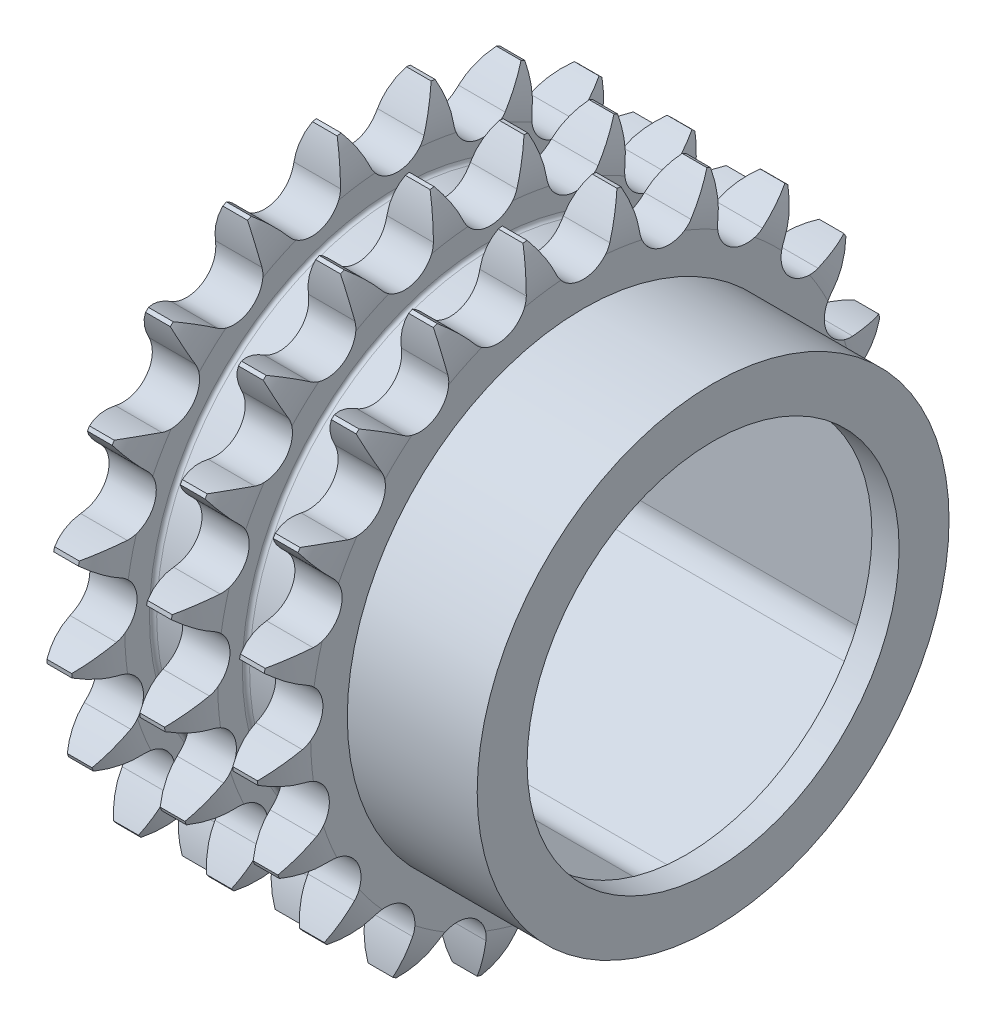
SolidWorks part; units mm, degrees
material "1.0503 (C45)"
ref_plane "Plane1" through (0, 0, 0) normal (0, 0, 1) x (1, 0, 0)
ref_plane "Plane2" through (0, 0, 0) normal (0, 1, 0) x (1, 0, 0)
ref_plane "Plane3" through (0, 0, 0) normal (1, 0, 0) x (0, 0, -1)
sketch "Clipboard" plane through (0, 0, 0) normal (0, 1, 0) x (1, 0, 0)
  line L0 (0, 0) -> (8.8924, -3.4135)
  line L1 (-15, 0) -> (100, 0) construction
  line L2 (0, 0) -> (-0.8203, 0.9272)
  line L3 (0, 0) -> (-8.8973, 3.4006)
  line L4 (0, 0) -> (2.8941, 1.1109)
  line L5 (0, 0) -> (-46.8476, -17.4728)
  line L6 (0, 0) -> (-21.2921, -14.3658)
  line L7 (-0.8203, 0.9272) -> (44.8574, 21.2642)
  line L8 (-76.2, 38.1) -> (-75.5, 38.1)
  line L9 (-73.319, 40.6764) -> (-72.9207, 40.7126)
  line L10 (-73.4529, 9.1872) -> (-63.2129, 9.1872)
  circle A0 centre (0, 0) radius 3.175
  circle A1 centre (0, 0) radius 26.8806
  circle A2 centre (0, 0) radius 37.5
  dimension "Dr" = 6.35
  dimension "MHD" = 53.7612
  dimension "Hub_dia" = 75
  dimension "Num_teeth" = 21
  dimension "Pitch" = 9.525
  dimension "Width" = 3.1
  dimension "Side_relief" = 1.238
  dimension "Side_radius" = 9.525
  dimension "Overall_len" = 50
  dimension "Show_teeth" = 21
  dimension "Thickness" = 25.6852
  dimension "OAL" = 50.0005
  dimension "T_dim" = 0.7
  dimension "Fillet_rad" = 0.4
  dimension "Face_width" = 5.205
  dimension "Num_strands" = 3
  dimension "Transv_pitch" = 10.24
  dimension "Plate_wid" = 8.26
sketch "BasProSke" plane through (0, 0, 0) normal (0, 1, 0) x (1, 0, 0)
  line L0 (-10, 0) -> (60, 0) construction
  line L1 (0, 0) -> (0, 30.0363)
  line L2 (0, 0) -> (25.6852, 0)
  line L3 (25.6852, 0) -> (25.6852, 30.0363)
  line L4 (24.4472, 34.7321) -> (1.238, 34.7321)
  arc A0 (0, 30.0363) -> (1.238, 34.7321) centre (9.525, 30.0363) cw
  arc A1 (25.6852, 30.0363) -> (24.4472, 34.7321) centre (16.1602, 30.0363) ccw
  dimension "Thickness" = 25.6852
  dimension "D1" = 9.525
  dimension "G1" = 1.238
  dimension "G2" = 1.238
  dimension "Diameter" = 69.4643
revolve "Base-Revolve" add sketch "BasProSke" angle 360 about L0
sketch "GrvSke" plane through (0, 0, 0) normal (0, 1, 0) x (1, 0, 0)
  line L0 (5.2052, 30.0363) -> (5.2052, 27.3219)
  line L1 (5.6052, 26.9219) -> (9.84, 26.9219)
  line L2 (10.24, 27.3219) -> (10.24, 30.0363)
  line L3 (3.9672, 34.7321) -> (11.478, 34.7321)
  line L4 (7.7226, 0) -> (7.7226, 52.07) construction
  line L5 (-10, 0) -> (60, 0) construction
  line L6 (0, 0) -> (35.56, 0) construction
  arc A0 (10.24, 30.0363) -> (11.478, 34.7321) centre (19.765, 30.0363) cw
  arc A1 (5.2052, 30.0363) -> (3.9672, 34.7321) centre (-4.3198, 30.0363) ccw
  arc A2 (5.2052, 27.3219) -> (5.6052, 26.9219) centre (5.6052, 27.3219) ccw
  arc A3 (9.84, 26.9219) -> (10.24, 27.3219) centre (9.84, 27.3219) ccw
  dimension "Fillet_rad" = 0.4
  dimension "D1" = 9.525
  dimension "G1" = 1.238
  dimension "Diameter" = 69.4643
  dimension "Grv_diam" = 53.8438
  dimension "Offset" = 7.7226
  dimension "Grv_width" = 5.0348
revolve "Groove" cut sketch "GrvSke" angle 360 about L6
pattern_linear "Grooves" count 2 spacing 10.24 along (1, 0, 0) of "Groove"
sketch "TooCutSke" plane through (0, 0, 0) normal (1, 0, 0) x (0, 0, -1)
  line L0 (0, 31.9858) -> (2.9702, 30.7771) construction
  line L1 (0, 0) -> (0, 107) construction
  line L2 (0, 31.9858) -> (-10, 31.9858) construction
  line L3 (0, 31.9858) -> (-2.9702, 30.7771) construction
  arc A0 (2.9702, 30.7771) -> (5.2931, 34.8323) centre (19.2036, 24.1712) cw
  arc A1 (2.9702, 30.7771) -> (-2.9702, 30.7771) centre (0, 31.9858) cw
  arc A2 (-2.9702, 30.7771) -> (-5.2931, 34.8323) centre (-19.2036, 24.1712) ccw
  arc A3 (5.2931, 34.8323) -> (-5.2931, 34.8323) centre (0, 0) ccw
  dimension "R1" = 3.2067
  dimension "R2" = 17.526
  dimension "Overcut" = 35.2321
  dimension "Seat_radius" = 31.9858
  dimension "X" = 135.714
extrude "ToothCut" cut sketch "TooCutSke" along normal through all
pattern_circular "TeethCuts" count 21 every 17.143 about axis through (-10, 0, 0) along (1, 0, 0) of "ToothCut"
sketch "HubNeaOneSke" plane through (0, 0, 0) normal (-1, 0, 0) x (0, 0, 1)
  circle A0 centre (0, 0) radius 26.8806
  dimension "Diameter" = 53.7612
extrude "HubNearOne" [suppressed] add sketch "HubNeaOneSke" along normal blind 24.3153
fillet "HubNearOneFillet" [suppressed] radius 0.4
sketch "HubNeaBotSke" plane through (0, 0, 0) normal (-1, 0, 0) x (0, 0, 1)
  circle A0 centre (0, 0) radius 26.8806
  dimension "Diameter" = 53.7612
extrude "HubNearBoth" [suppressed] add sketch "HubNeaBotSke" along normal blind 12.1577
fillet "HubNearBothFillet" [suppressed] radius 0.4
ref_plane "FarPln" through (25.6852, 0, 0) normal (1, 0, 0) x (0, 0, -1)
sketch "HubFarSke" plane through (25.6852, 0, 0) normal (1, 0, 0) x (0, 0, -1)
  circle A0 centre (0, 0) radius 26.8806
  dimension "Diameter" = 53.7612
extrude "HubFar" [suppressed] add sketch "HubFarSke" along normal blind 12.1577
fillet "HubFarFillet" [suppressed] radius 0.4
sketch "BorSke" plane through (0, 0, 0) normal (1, 0, 0) x (0, 0, -1)
  circle A0 centre (0, 0) radius 2
  dimension "Diameter" = 4
extrude "Bore" cut sketch "BorSke" along normal mid plane 100.001
sketch "KeySke" plane through (0, 0, 0) normal (1, 0, 0) x (0, 0, -1)
  line L0 (-0.8, 0) -> (-0.8, 2.7)
  line L1 (-0.8, 2.7) -> (0.8, 2.7)
  line L2 (0.8, 2.7) -> (0.8, 0)
  line L3 (0, 0) -> (0, 34) construction
  line L4 (-0.8, 0) -> (0.8, 0)
  dimension "Offset" = 2.7
  dimension "Width" = 1.6
extrude "Keyway" [suppressed] cut sketch "KeySke" along normal mid plane 100.001
pattern_circular "Keyway2" [suppressed] count 2 every 90 about axis through (-10, 0, 0) along (1, 0, 0)
sketch "Sketch1" plane through (25.6852, 0, 0) normal (1, 0, 0) x (0, 0, -1)
  line L1 (-21.5, -12.413) -> (0, -24.8261)
  line L2 (0, -24.8261) -> (21.5, -12.413)
  line L3 (21.5, -12.413) -> (21.5, 12.413)
  line L4 (21.5, 12.413) -> (0, 24.8261)
  line L5 (0, 24.8261) -> (-21.5, 12.413)
  line L6 (-21.5, 12.413) -> (-21.5, -12.413)
  circle A0 centre (0, 0) radius 21.5 construction
  dimension "D1" = 43
extrude "Cut-Extrude1" cut sketch "Sketch1" against normal through all
fillet "Fillet1" radius 3 6 edges at (12.8426, 24.8261, 0) (12.8426, 12.413, 21.5) (12.8426, -12.413, 21.5) (12.8426, -24.8261, 0) (12.8426, -12.413, -21.5) (12.8426, 12.413, -21.5)
sketch "Sketch2" plane through (25.6852, 0, 0) normal (1, 0, 0) x (0, 0, -1)
  line L7 (-20, -13.2791) -> (-1.5, -23.96)
  line L8 (-21.5, 10.681) -> (-21.5, -10.681)
  line L9 (-1.5, 23.96) -> (-20, 13.2791)
  line L10 (20, 13.2791) -> (1.5, 23.96)
  line L11 (21.5, -10.681) -> (21.5, 10.681)
  line L12 (1.5, -23.96) -> (20, -13.2791)
  line L13 (-20, -13.2791) -> (-1.5, -23.96)
  line L14 (-21.5, 10.681) -> (-21.5, -10.681)
  line L15 (-1.5, 23.96) -> (-20, 13.2791)
  line L16 (20, 13.2791) -> (1.5, 23.96)
  line L17 (21.5, -10.681) -> (21.5, 10.681)
  line L18 (1.5, -23.96) -> (20, -13.2791)
  circle A0 centre (0, 0) radius 26
  arc A6 (-21.5, -10.681) -> (-20, -13.2791) centre (-18.5, -10.681) ccw
  arc A7 (-20, 13.2791) -> (-21.5, 10.681) centre (-18.5, 10.681) ccw
  arc A8 (1.5, 23.96) -> (-1.5, 23.96) centre (0, 21.362) ccw
  arc A9 (21.5, 10.681) -> (20, 13.2791) centre (18.5, 10.681) ccw
  arc A10 (20, -13.2791) -> (21.5, -10.681) centre (18.5, -10.681) ccw
  arc A11 (-1.5, -23.96) -> (1.5, -23.96) centre (0, -21.362) ccw
  arc A12 (-21.5, -10.681) -> (-20, -13.2791) centre (-18.5, -10.681) ccw
  arc A13 (-20, 13.2791) -> (-21.5, 10.681) centre (-18.5, 10.681) ccw
  arc A14 (1.5, 23.96) -> (-1.5, 23.96) centre (0, 21.362) ccw
  arc A15 (21.5, 10.681) -> (20, 13.2791) centre (18.5, 10.681) ccw
  arc A16 (20, -13.2791) -> (21.5, -10.681) centre (18.5, -10.681) ccw
  arc A17 (-1.5, -23.96) -> (1.5, -23.96) centre (0, -21.362) ccw
  dimension "D2" = 52
  dimension "D1" = 0
extrude "Boss-Extrude1" add sketch "Sketch2" along normal offset from surface (14.3148 mm away) 40 up to face at (0, 0, 0)
sketch "Sketch3" plane through (0, 0, 0) normal (1, 0, 0) x (0, 0, -1)
  circle A0 centre (0, 0) radius 26 construction
  circle A1 centre (0, 0) radius 26
  circle A2 centre (0, 0) radius 20.5
  dimension "D1" = 41
extrude "Boss-Extrude2" add sketch "Sketch3" against normal blind 3 from vertex
equation "' \"Pitch@Clipboard\" = 12.7"
equation "' \"Num_strands@Clipboard\" = 3"
equation "' \"Num_teeth@Clipboard\" = 9"
equation "' \"Hub_dia@Clipboard\" = 50"
equation "' \"Overall_len@Clipboard\" = 3"
equation "' \"Diameter@BorSke\" = 12"
equation "' \"T_dim@Clipboard\" = 1"
equation "' \"Width@KeySke\" = 2"
equation "' \"Dr@Clipboard\" = 8.51"
equation "' \"Face_width@Clipboard\" = 7.2"
equation "' \"Side_radius@Clipboard\" = 12.7"
equation "' \"Side_relief@Clipboard\" = 1.27"
equation "' \"Transv_pitch@Clipboard\" = 13.92"
equation "' \"Show_teeth@Clipboard\" = 9"
equation "' \"Fillet_rad@Clipboard\" = 0.6"
equation "' \"Plate_wid@Clipboard\" = 11.8"
equation "\"Num_teeth@Clipboard\" = int( \"Num_teeth@Clipboard\" )"
equation "\"Num_teeth@Clipboard\" = ((sgn( \"Num_teeth@Clipboard\" - 5.0)+1)*( \"Num_teeth@Clipboard\" - 5.0))/2 +5.0"
equation "\"Num_teeth@Clipboard\" = ((sgn( \"Num_teeth@Clipboard\" - 200.0)-1)*( \"Num_teeth@Clipboard\" - 200.0))/-2 +200.0"
equation "\"MHD@Clipboard\" = \"Pitch@Clipboard\" * (1.0 / tan(3.14159265 / \"Num_teeth@Clipboard\" )) - 1.05 * \"Plate_wid@Clipboard\" - 0.76"
equation "\"Thickness@Clipboard\"  = \"Face_width@Clipboard\" + (\"Num_strands@Clipboard\" - 1) * \"Transv_pitch@Clipboard\""
equation "\"OAL@Clipboard\" = \"Thickness@Clipboard\" + 2 * \"Fillet_rad@Clipboard\" + 1"
equation "\"MHD@Clipboard\" = ((sgn( \"MHD@Clipboard\" - \"Hub_dia@Clipboard\" )-1)*( \"MHD@Clipboard\" - \"Hub_dia@Clipboard\" ))/-2+ \"Hub_dia@Clipboard\""
equation "\"OAL@Clipboard\" = ((sgn( \"OAL@Clipboard\" - \"Overall_len@Clipboard\" )+1)*( \"OAL@Clipboard\" - \"Overall_len@Clipboard\" ))/2 + \"Overall_len@Clipboard\" + 0.0005"
equation "\"Num_teeth@TeethCuts\" = int( \"Show_teeth@Clipboard\" ) + 1"
equation "\"Num_teeth@TeethCuts\" = ((sgn( \"Num_teeth@TeethCuts\" - \"Num_teeth@Clipboard\" )-1)*( \"Num_teeth@TeethCuts\" - \"Num_teeth@Clipboard\" ))/-2+ \"Num_teeth@Clipboard\""
equation "\"Num_teeth@TeethCuts\" = ((sgn( \"Num_teeth@TeethCuts\" - 2.0)+1)*( \"Num_teeth@TeethCuts\" - 2.0))/2 +2.0"
equation "\"Angle@TeethCuts\" = 360.0 / \"Num_teeth@Clipboard\""
equation "\"Seat_radius@TooCutSke\" = ( \"Pitch@Clipboard\" / 2.0) / sin(3.14159265 / \"Num_teeth@Clipboard\" ) - \"Dr@Clipboard\" / 2.0 + \"Dr@Clipboard\" * 0.505"
equation "\"R1@TooCutSke\"  = \"Dr@Clipboard\" * 0.505"
equation "\"X@TooCutSke\" = 140.0 - (90.0 / \"Num_teeth@Clipboard\")"
equation "\"R2@TooCutSke\" = 0.12 * \"Dr@Clipboard\" * ( \"Num_teeth@Clipboard\" + 2.0)"
equation "\"Overcut@TooCutSke\" = 0.5 + 0.625 * \"Pitch@Clipboard\" - 0.5 * \"Dr@Clipboard\"  +  \"Pitch@Clipboard\" / 2.0 / sin(3.14159265 / \"Num_teeth@Clipboard\" )"
equation "\"Diameter@BasProSke\" = 2.0 * ( 0.625 * \"Pitch@Clipboard\" - 0.5 * \"Dr@Clipboard\"  +  \"Pitch@Clipboard\" / 2.0 / sin(3.14159265 / \"Num_teeth@Clipboard\" ))"
equation "\"Thickness@BasProSke\"  = \"Thickness@Clipboard\""
equation "\"G1@BasProSke\" =  \"Side_relief@Clipboard\""
equation "\"G2@BasProSke\" =  \"Side_relief@Clipboard\""
equation "\"D1@BasProSke\" =  \"Side_radius@Clipboard\""
equation "\"Diameter@GrvSke\" = \"Diameter@BasProSke\""
equation "\"G1@GrvSke\" = \"Side_relief@Clipboard\""
equation "\"D1@GrvSke\" = \"Side_radius@Clipboard\""
equation "\"Grv_diam@GrvSke\" =  \"Pitch@Clipboard\" * (1.0 / tan(3.14159265 / \"Num_teeth@Clipboard\" ))- 1.04 * \"Plate_wid@Clipboard\" - 0.76"
equation "\"Grv_width@GrvSke\" =  \"Transv_pitch@Clipboard\" - \"Face_width@Clipboard\""
equation "\"Offset@GrvSke\" = \"Grv_width@GrvSke\" / 2.0 + \"Face_width@Clipboard\""
equation "\"Fillet_rad@GrvSke\" = \"Fillet_rad@Clipboard\""
equation "\"Offset@Grooves\" = \"Transv_pitch@Clipboard\""
equation "\"Num_grvs@Grooves\" = \"Num_strands@Clipboard\""
equation "\"Num_grvs@Grooves\" = \"Num_grvs@Grooves\" - 1 * sgn( \"Num_grvs@Grooves\" -1)"
equation "\"Diameter@HubNeaOneSke\" = \"MHD@Clipboard\""
equation "\"Length@HubNearOne\" = \"OAL@Clipboard\" - \"Thickness@BasProSke\""
equation "\"Diameter@HubNeaBotSke\" = \"MHD@Clipboard\""
equation "\"Length@HubNearBoth\" = ( \"OAL@Clipboard\" - \"Thickness@BasProSke\" ) / 2.0"
equation "\"D1@HubNearOneFillet\" = \"Fillet_rad@Clipboard\""
equation "\"D1@HubNearBothFillet\" = \"Fillet_rad@Clipboard\""
equation "\"Thickness@FarPln\" = \"Thickness@BasProSke\""
equation "\"Diameter@HubFarSke\" = \"MHD@Clipboard\""
equation "\"Length@HubFar\" = ( \"OAL@Clipboard\" - \"Thickness@BasProSke\" ) / 2.0"
equation "\"D1@HubFarFillet\" = \"Fillet_rad@Clipboard\""
equation "\"D1@Bore\" = \"OAL@Clipboard\" * 2.0"
equation "\"D1@Keyway\" = \"OAL@Clipboard\" * 2.0"
equation "\"Offset@KeySke\" = \"T_dim@Clipboard\" + \"Diameter@BorSke\" / 2.0"
